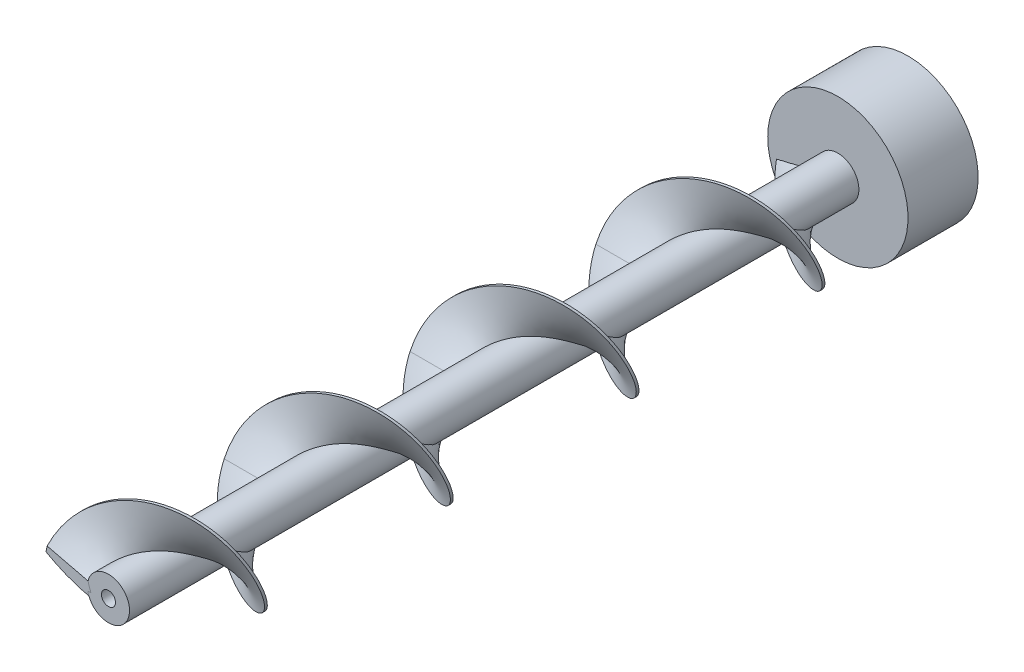
SolidWorks part; units mm, degrees
ref_plane "Спереди" through (0, 0, 0) normal (0, 0, 1) x (1, 0, 0)
ref_plane "Сверху" through (0, 0, 0) normal (0, 1, 0) x (1, 0, 0)
ref_plane "Справа" through (0, 0, 0) normal (1, 0, 0) x (0, 0, -1)
sketch "Эскиз2" plane through (0, 0, 0) normal (0, 0, 1) x (1, 0, 0)
  circle A0 centre (0, 0) radius 3
  circle A1 centre (0, 0) radius 1
  dimension "D1" = 2
  dimension "D2" = 2
  dimension "D3" = 6
extrude "Бобышка-Вытянуть2" add sketch "Эскиз2" along normal blind 105
sketch "Эскиз3" plane through (0, 0, 0) normal (0, 0, -1) x (-1, 0, 0)
  circle A0 centre (0, 0) radius 10
  dimension "D1" = 20
extrude "Бобышка-Вытянуть3" add sketch "Эскиз3" along normal blind 10
sketch "Эскиз27" plane through (0, 0, 105) normal (0, 0, 1) x (1, 0, 0)
  circle A0 centre (0, 0) radius 3 construction
  circle A1 centre (0, 0) radius 3
curve "Спираль2" pitch 26.5 height 26.5 radius 3 centre (0, 0, 105) axis (0, 0, -1) start towards (-1, 0, 0)
ref_plane "Плоскость2" through (-3, 0, 105) normal (0, 0.5796, -0.8149) x (1, 0, 0)
sketch "Эскиз28" plane through (-3, 0, 105) normal (0, 0.5796, -0.8149) x (1, 0, 0)
  line L0 (0.9599, 1.6) -> (0, 0)
  line L1 (0, 0) -> (-6, 0)
  line L3 (-6, 0.4) -> (0.9599, 1.6)
  line L4 (-6, 0) -> (-6, 0.4)
  dimension "D1" = 0.4
  dimension "D2" = 1.6
  dimension "D3" = 6
  dimension "D4" = 6.9599
sweep "По траектории2" add profiles "Эскиз28" path "Спираль2"
sketch3d "Трехмерный эскиз11"
  spline S0 degree 2 poles (7.4493, -5.0505, 106.2499) (-24.8524, -52.6944, 130.5866) (-8.6354, 2.5356, 103.7955) (-8.2709, 3.7772, 103.1932) (-7.5713, 4.8658, 102.5909) (-6.8717, 5.9544, 101.9886) (-5.8937, 6.8017, 101.3864) (-4.9158, 7.6491, 100.7841) (-3.7387, 8.1867, 100.1818) (-2.5617, 8.7242, 99.5795) (-1.2808, 8.9084, 98.9773) (0, 9.0925, 98.375) (1.2808, 8.9084, 97.7727) (2.5617, 8.7242, 97.1705) (3.7387, 8.1867, 96.5682) (4.9158, 7.6491, 95.9659) (5.8937, 6.8017, 95.3636) (6.8717, 5.9544, 94.7614) (7.5713, 4.8658, 94.1591) (8.2709, 3.7772, 93.5568) (8.6354, 2.5356, 92.9545) (9, 1.294, 92.3523) (9, 0, 91.75) (9, -1.294, 91.1477) (8.6354, -2.5356, 90.5455) (8.2709, -3.7772, 89.9432) (7.5713, -4.8658, 89.3409) (6.8717, -5.9544, 88.7386) (5.8937, -6.8017, 88.1364) (4.9158, -7.6491, 87.5341) (3.7387, -8.1867, 86.9318) (2.5617, -8.7242, 86.3295) (1.2808, -8.9084, 85.7273) (0, -9.0925, 85.125) (-1.2808, -8.9084, 84.5227) (-2.5617, -8.7242, 83.9205) (-3.7387, -8.1867, 83.3182) (-4.9158, -7.6491, 82.7159) (-5.8937, -6.8017, 82.1136) (-6.8717, -5.9544, 81.5114) (-7.5713, -4.8658, 80.9091) (-8.2709, -3.7772, 80.3068) (-8.6354, -2.5356, 79.7045) (-29.1189, 67.2246, 45.8651) (7.7565, 4.5647, 77.4968) knots -1.356163 -1.356163 -1.356163 0.045455 0.045455 0.090909 0.090909 0.136364 0.136364 0.181818 0.181818 0.227273 0.227273 0.272727 0.272727 0.318182 0.318182 0.363636 0.363636 0.409091 0.409091 0.454545 0.454545 0.5 0.5 0.545455 0.545455 0.590909 0.590909 0.636364 0.636364 0.681818 0.681818 0.727273 0.727273 0.772727 0.772727 0.818182 0.818182 0.863636 0.863636 0.909091 0.909091 0.954545 0.954545 2.589874 2.589874 2.589874 weights 19.728503 0.686138 1 0.989821 1 0.989821 1 0.989821 1 0.989821 1 0.989821 1 0.989821 1 0.989821 1 0.989821 1 0.989821 1 0.989821 1 0.989821 1 0.989821 1 0.989821 1 0.989821 1 0.989821 1 0.989821 1 0.989821 1 0.989821 1 0.989821 1 0.989821 1 0.633804 26.617078 only from (-9, 0, 105) to (-9, 0, 78.5) construction
  spline S1 degree 2 poles (-9, 0, 105) (-9, 1.294, 104.3977) (-8.6354, 2.5356, 103.7955) (-8.2709, 3.7772, 103.1932) (-7.5713, 4.8658, 102.5909) (-6.8717, 5.9544, 101.9886) (-5.8937, 6.8017, 101.3864) (-4.9158, 7.6491, 100.7841) (-3.7387, 8.1867, 100.1818) (-2.5617, 8.7242, 99.5795) (-1.2808, 8.9084, 98.9773) (0, 9.0925, 98.375) (1.2808, 8.9084, 97.7727) (2.5617, 8.7242, 97.1705) (3.7387, 8.1867, 96.5682) (4.9158, 7.6491, 95.9659) (5.8937, 6.8017, 95.3636) (6.8717, 5.9544, 94.7614) (7.5713, 4.8658, 94.1591) (8.2709, 3.7772, 93.5568) (8.6354, 2.5356, 92.9545) (9, 1.294, 92.3523) (9, 0, 91.75) (9, -1.294, 91.1477) (8.6354, -2.5356, 90.5455) (8.2709, -3.7772, 89.9432) (7.5713, -4.8658, 89.3409) (6.8717, -5.9544, 88.7386) (5.8937, -6.8017, 88.1364) (4.9158, -7.6491, 87.5341) (3.7387, -8.1867, 86.9318) (2.5617, -8.7242, 86.3295) (1.2808, -8.9084, 85.7273) (0, -9.0925, 85.125) (-1.2808, -8.9084, 84.5227) (-2.5617, -8.7242, 83.9205) (-3.7387, -8.1867, 83.3182) (-4.9158, -7.6491, 82.7159) (-5.8937, -6.8017, 82.1136) (-6.8717, -5.9544, 81.5114) (-7.5713, -4.8658, 80.9091) (-8.2709, -3.7772, 80.3068) (-8.6354, -2.5356, 79.7045) (-9, -1.294, 79.1023) (-9, 0, 78.5) knots 0 0 0 0.045455 0.045455 0.090909 0.090909 0.136364 0.136364 0.181818 0.181818 0.227273 0.227273 0.272727 0.272727 0.318182 0.318182 0.363636 0.363636 0.409091 0.409091 0.454545 0.454545 0.5 0.5 0.545455 0.545455 0.590909 0.590909 0.636364 0.636364 0.681818 0.681818 0.727273 0.727273 0.772727 0.772727 0.818182 0.818182 0.863636 0.863636 0.909091 0.909091 0.954545 0.954545 1 1 1 weights 1 0.989821 1 0.989821 1 0.989821 1 0.989821 1 0.989821 1 0.989821 1 0.989821 1 0.989821 1 0.989821 1 0.989821 1 0.989821 1 0.989821 1 0.989821 1 0.989821 1 0.989821 1 0.989821 1 0.989821 1 0.989821 1 0.989821 1 0.989821 1 0.989821 1 0.989821 1
sketch3d "Трехмерный эскиз12"
  spline S0 degree 3 poles (713.9155, 1861.3659, 3.578) (101.6066, -76.8433, 148.6158) (-11.5565, -11.855, 124.9607) (-2.1765, 2.1764, 101.6876) (-1.1779, 2.8438, 100.0312) (0, 3.0781, 98.375) (1.1779, 2.8438, 96.7187) (2.1765, 2.1765, 95.0625) (2.8438, 1.1779, 93.4062) (3.0781, 0, 91.75) (2.8438, -1.1779, 90.0938) (2.1765, -2.1765, 88.4375) (1.1779, -2.8438, 86.7813) (0, -3.0781, 85.125) (-1.1779, -2.8438, 83.4688) (-2.1765, -2.1764, 81.8124) (-11.5566, 11.8552, 58.539) (101.6098, 76.8451, 34.8835) (713.9422, -1861.4503, 179.9284) knots -2.4483 -2.4483 -2.4483 -2.4483 0.0625 0.125 0.1875 0.25 0.3125 0.375 0.4375 0.5 0.5625 0.625 0.6875 0.75 0.8125 0.875 0.9375 3.448336 3.448336 3.448336 3.448336 only from (-3, 0, 105) to (-3, 0, 78.5) construction
  spline S1 degree 3 poles (-3, 0, 105) (-3, 0.3919, 104.4491) (-2.8438, 1.1783, 103.3432) (-2.1765, 2.1764, 101.6876) (-1.1779, 2.8438, 100.0312) (0, 3.0781, 98.375) (1.1779, 2.8438, 96.7187) (2.1765, 2.1765, 95.0625) (2.8438, 1.1779, 93.4062) (3.0781, 0, 91.75) (2.8438, -1.1779, 90.0938) (2.1765, -2.1765, 88.4375) (1.1779, -2.8438, 86.7813) (0, -3.0781, 85.125) (-1.1779, -2.8438, 83.4688) (-2.1765, -2.1764, 81.8124) (-2.8438, -1.1783, 80.1568) (-3, -0.3919, 79.0509) (-3, 0, 78.5) knots 0 0 0 0 0.0625 0.125 0.1875 0.25 0.3125 0.375 0.4375 0.5 0.5625 0.625 0.6875 0.75 0.8125 0.875 0.9375 1 1 1 1
pattern_linear "Линейный массив6" count 4 spacing 26.5 along (0, 0, -1) of bodies 109
sketch "Эскиз38" plane through (0, 0, -10) normal (0, 0, -1) x (-1, 0, 0)
  line L0 (-14.6163, 0) -> (10.1711, 0) construction
  line L1 (0, 1.4943) -> (0, -5.3618) construction
  circle A0 centre (3.5, 3.5) radius 2.5
  circle A1 centre (3.5, -3.5) radius 2.5
  circle A2 centre (-3.5, -3.5) radius 2.5
  circle A3 centre (-3.5, 3.5) radius 2.5
  point P3 (0, 0)
  point P6 (0, 0)
  point P12 (-5.1553, 4.0809)
  point P16 (0, 4.4406)
  point P17 (3.6226, 4.4406)
  point P18 (-3.6226, 4.1086)
  point P19 (0, 0)
  point P20 (0, 0)
  point P21 (0, 0)
  point P22 (0, 0)
  point P23 (3.5892, 3.2051)
  point P24 (0, 0)
  point P25 (0, 0)
  point P28 (3.8582, 3.5475)
  dimension "D1" = 7
  dimension "D2" = 7
  dimension "D4" = 5
  dimension "D6" = 5
  dimension "D3" = 5
  dimension "D5" = 5
extrude "Вырез-Вытянуть1" cut sketch "Эскиз38" against normal blind 8
sketch "Эскиз39" plane through (0, 0, 105) normal (0, 0, 1) x (1, 0, 0)
  circle A0 centre (0, 0) radius 10.1868
extrude "Вырез-Вытянуть2" cut sketch "Эскиз39" against normal blind 1
sketch "Эскиз40" plane through (0, 0, 104) normal (0, 0, 1) x (1, 0, 0)
  circle A0 centre (0, 0) radius 9.8815
